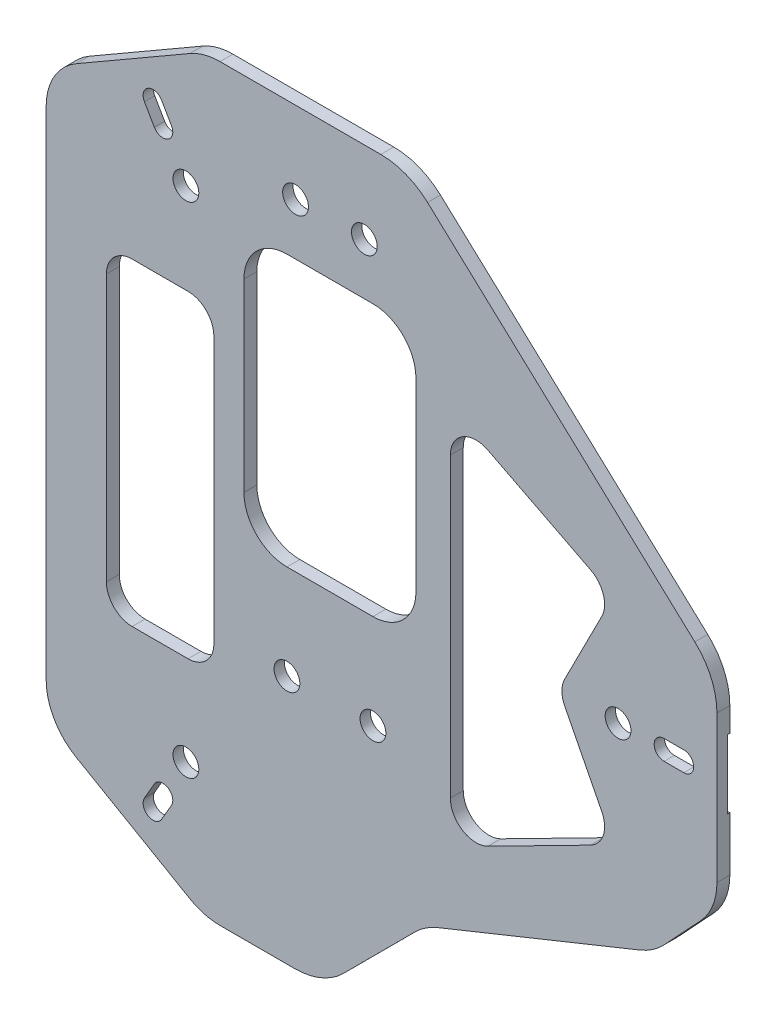
SolidWorks part; units mm, degrees
material "Custom Plastic"
ref_plane "Front Plane" through (0, 0, 0) normal (0, 0, 1) x (1, 0, 0)
ref_plane "Top Plane" through (0, 0, 0) normal (0, 1, 0) x (1, 0, 0)
ref_plane "Right Plane" through (0, 0, 0) normal (1, 0, 0) x (0, 0, -1)
ref_axis "Axis_Symmetry" through (0, 0, -0.825) along (0, 0, 1)
sketch "Center" plane through (0, 0, 0) normal (0, 0, 1) x (1, 0, 0)
  line L0 (0, 0) -> (33.5, 0)
  line L1 (0, 0) -> (-16.75, 29.0119)
  line L2 (0, 0) -> (-16.75, -29.0119)
  circle A0 centre (0, 0) radius 33.5
  dimension "D1" = 67
  dimension "D2" = 120
  dimension "D3" = 120
sketch "Borders" plane through (0, 0, 0) normal (0, 0, 1) x (1, 0, 0)
  line L0 (45, 43.5) -> (45, -43.5)
  line L1 (45, -43.5) -> (-33, -43.5)
  line L2 (-33, -43.5) -> (-33, 43.5)
  line L3 (-33, 43.5) -> (45, 43.5)
  dimension "D1" = 33
  dimension "D2" = 45
  dimension "D3" = 43.5
  dimension "D4" = 43.5
sketch "Sketch3" plane through (0, 0, 0) normal (0, 0, 1) x (1, 0, 0)
  line L0 (0, 0) -> (-33, 0)
  line L1 (-33, -43.5) -> (-33, 43.5) construction
  line L2 (-33, 0) -> (-33, 32.91)
  line L3 (-33, 0) -> (-33, -32.91)
  line L4 (-33, -32.91) -> (-14.6576, -43.5)
  line L5 (45, -43.5) -> (-33, -43.5) construction
  line L6 (-14.6576, -43.5) -> (9.0524, -43.5)
  line L7 (9.0524, -43.5) -> (45, -10.2901)
  line L8 (45, 43.5) -> (45, -43.5) construction
  line L9 (45, -10.2901) -> (45, 13.0399)
  line L10 (45, 13.0399) -> (37.6617, 20.9092)
  line L12 (-33, 32.91) -> (-14.6576, 43.5)
  line L14 (-33, 43.5) -> (45, 43.5) construction
  line L15 (-14.6576, 43.5) -> (-0.7776, 43.5)
  line L16 (-0.7776, 43.5) -> (11.048, 31.6516)
  line L17 (11.048, 31.6516) -> (37.6617, 20.9092)
  point P25 (45, 13.0399)
  point P28 (37.6617, 20.9092)
  point P31 (11.048, 31.6516)
  point P34 (-0.7776, 43.5)
  point P37 (-14.6576, 43.5)
  dimension "D12" = 32.91
  dimension "D13" = 137
  dimension "D2" = 21.18
  dimension "D3" = 23.71
  dimension "D4" = 48.94
  dimension "D5" = 23.33
  dimension "D6" = 21.18
  dimension "D7" = 13.88
  dimension "D8" = 16.74
  dimension "D9" = 28.7
  dimension "D10" = 10.76
  dimension "D11" = 32.91
extrude "Boss-Extrude1" add sketch "Sketch3" along normal blind 0.75 and the other way blind 0.75 contours L2 L12 L15 L16 L17 L10 L9 L7 L6 L4 L3
fillet "Corner_Radius_7" radius 7 5 edges at (45, 13.0399, 0) (-33, 32.91, 0) (-14.6576, 43.5, 0) (-14.6576, -43.5, 0) (-33, -32.91, 0)
fillet "Corner_Radius_8" radius 8 5 edges at (9.0524, -43.5, 0) (45, -10.2901, 0) (37.6617, 20.9092, 0) (-0.7776, 43.5, 0) (11.048, 31.6516, 0)
move or copy body "Align_axis_remage" bodies to move or copy 101 copy no rotation origin (0, 0, 0) rotation axis (1, 0, 0) rotation angle 180
sketch "Sketch5" plane through (0, 0, -0.75) normal (0, 0, 1) x (1, 0, 0)
  line L0 (0, 0) -> (33.5, 0)
  line L1 (0, 0) -> (-16.75, 29.0119)
  line L2 (0, 0) -> (-16.75, -29.0119)
  line L3 (33.5, 0) -> (45, 0)
  line L4 (45, 6.7895) -> (45, -10.2825) construction
  line L5 (45, 4) -> (31.5, 4)
  line L6 (30, 2.5) -> (30, -2.5)
  line L7 (31.5, -4) -> (45, -4)
  line L8 (45, 4) -> (45, -4)
  circle A0 centre (0, 0) radius 33.5
  arc A5 (30, -2.5) -> (31.5, -4) centre (31.5, -2.5) ccw
  arc A6 (31.5, 4) -> (30, 2.5) centre (31.5, 2.5) ccw
  line M39 (45, 6.7895) -> (45, -10.2825)
  dimension "D1" = 67
  dimension "D2" = 120
  dimension "D8" = 1.5
  dimension "D3" = 120
  dimension "D5" = 4
  dimension "D6" = 4
  dimension "D7" = 15
extrude "Grooves" cut sketch "Sketch5" along normal blind 0.3 contours L7 A0 L3 M39 | L3 A0 L5 M39 | A5 L6 L0 A0 L7 | A6 L5 A0 L0 L6 region at (31.7612, 1.9149, -0.75) region at (31.7612, -1.9149, -0.75) region at (39.2099, 2.0069, -0.75) region at (39.2099, -2.0069, -0.75)
sketch "Sketch6" plane through (0, 0, 0.75) normal (0, 0, 1) x (1, 0, 0)
  line L0 (38.85, 0) -> (41.15, 0)
  line L1 (38.85, -1.15) -> (41.15, -1.15)
  line L2 (38.85, 1.15) -> (41.15, 1.15)
  circle A0 centre (33.5, 0) radius 1.5
  arc A1 (38.85, -1.15) -> (38.85, 1.15) centre (38.85, 0) cw
  arc A2 (41.15, -1.15) -> (41.15, 1.15) centre (41.15, 0) ccw
  point P0 (33.5, 0)
  dimension "D1" = 3
  dimension "D2" = 5.35
  dimension "D3" = 2.3
  dimension "D4" = 1.15
  dimension "D5" = 1.15
extrude "CopperRod_Holes" cut sketch "Sketch6" against normal up to next contours L1 A2 L2 A1 | A0 region at (37.7514, 0, 0.75) region at (33.5, 0, 0.75)
pattern_circular "CirPattern1" count 3 over 360 about axis through (0, 0, -0.825) along (0, 0, 1) of "Grooves", "CopperRod_Holes"
sketch "Sketch7" plane through (0, 0, 0.75) normal (0, 0, 1) x (1, 0, 0)
  line L0 (-0.1063, 0) -> (49999.8937, 0) construction
  line L2 (-13.5, 18.5) -> (-13.5, -18.5)
  line L3 (-13.5, -18.5) -> (-26, -18.5)
  line L4 (-26, -18.5) -> (-26, 18.5)
  line L5 (-26, 18.5) -> (-13.5, 18.5)
  line L6 (14, 22.17) -> (14, -22.17)
  line L7 (14, -22.17) -> (32.9695, -12.5045)
  line L8 (32.9695, -12.5045) -> (26.6073, 0)
  line L9 (26.6073, 0) -> (32.9695, 12.5045)
  line L10 (32.9695, 12.5045) -> (14, 22.17)
  line L11 (10, 28) -> (10, -3.5)
  line L12 (10, -3.5) -> (-10, -3.5)
  line L13 (-10, -3.5) -> (-10, 28)
  line L14 (-10, 28) -> (10, 28)
  point P5 (0, 0)
  point P9 (-13.5, -18.5)
  point P14 (-26, -18.5)
  point P19 (-13.5, 18.5)
  dimension "D3" = 14.03
  dimension "D1" = 37
  dimension "D2" = 12.5
  dimension "D4" = 13.5
  dimension "D5" = 44.34
  dimension "D6" = 21.29
  dimension "D7" = 63
  dimension "D8" = 14
  dimension "D9" = 20
  dimension "D10" = 31.5
  dimension "D11" = 3.5
  dimension "D12" = 10
extrude "Cut-Outs" cut sketch "Sketch7" against normal up to next
fillet "Corner_CutOuts_3" radius 3 9 edges at (-26, -18.5, 0) (-13.5, -18.5, 0) (-26, 18.5, 0) (-13.5, 18.5, 0) (26.6073, 0, 0) (14, -22.17, 0) (14, 22.17, 0) (32.9695, -12.5045, 0) (32.9695, 12.5045, 0)
fillet "Corner_CutOuts_5" radius 5 4 edges at (-10, -3.5, 0) (10, -3.5, 0) (-10, 28, 0) (10, 28, 0)
sketch "CopperPinHoles_position" plane through (0, 0, -0.75) normal (0, 0, -1) x (-1, 0, 0)
  line L1 (0, 0) -> (-33.5, 0) construction
  line L2 (0, 0) -> (0, 50000) construction
  point P0 (-4, 34)
  point P1 (4, 34)
  point P7 (-5, -14.5)
  point P8 (5, -14.5)
  dimension "D1" = 34
  dimension "D2" = 14.5
  dimension "D3" = 8
  dimension "D4" = 10
hole_wizard "CBORE for M5 Hex Head Bolt1" positions "3DSketch1" profile "Sketch10" counterbore size "M5" standard "ANSI Metric" end condition through all
sketch3d "3DSketch1"
  point P0 (5, -14.5, -0.75)
  point P3 (-5, -14.5, -0.75)
  point P6 (4, 34, -0.75)
  point P9 (-4, 34, -0.75)
sketch "Sketch10" plane through (5, -14.5, -0.75) normal (1, 0, 0) x (0, 1, 0)
  line L0 (0, 0) -> (0, 1.5)
  line L1 (0, 1.5) -> (1.5, 1.5)
  line L3 (1.5, 1.5) -> (1.5, 0.3)
  line L4 (1.5, 0.3) -> (2.25, 0.3)
  line L5 (2.25, 0.3) -> (2.25, 0)
  line L7 (2.25, 0) -> (0, 0)
  line L11 (0, -6.35) -> (0, 107.95) construction
  dimension "Thru Hole Dia." = 3
  dimension "Thru Hole Depth" = 1.5
  dimension "C'Bore Dia." = 4.5
  dimension "C'Bore Depth" = 0.3
sketch "Sketch11" plane through (0, 0, 0) normal (0, 0, 1) x (1, 0, 0)
  line L0 (0, 0) -> (33.5, 0) construction
  line L1 (0, 0) -> (0, 24.5831) construction
  point P5 (0, 24.5831)
